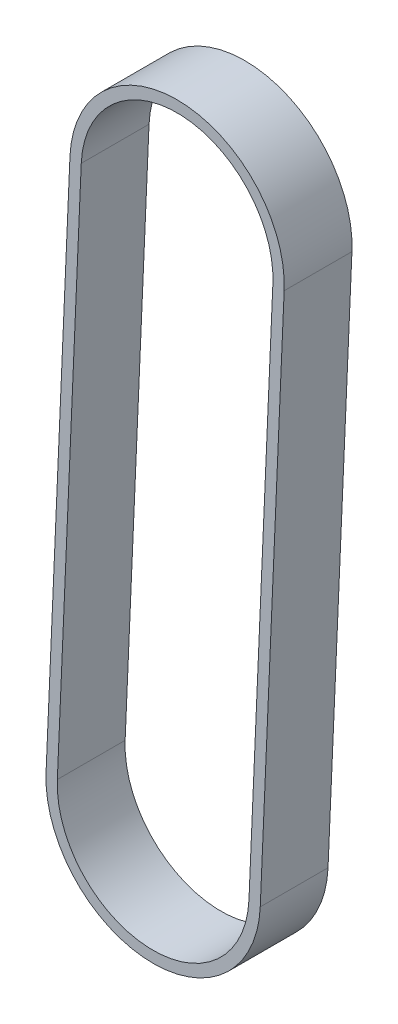
SolidWorks part; units mm, degrees
ref_plane "Front Plane" through (0, 0, 0) normal (0, 0, 1) x (1, 0, 0)
ref_plane "Top Plane" through (0, 0, 0) normal (0, 1, 0) x (1, 0, 0)
ref_plane "Right Plane" through (0, 0, 0) normal (1, 0, 0) x (0, 0, -1)
sketch "Sketch2" plane through (0, 0, 0) normal (0, 0, 1) x (1, 0, 0)
  line L0 (0, 0) -> (1, 0) construction
  line L1 (0, 0) -> (0, 1) construction
  line L2 (12.7202, -0.5576) -> (9.5452, -72.988)
  line L3 (-15.8952, -71.8729) -> (-12.7202, 0.5576)
  arc A0 (-12.7202, 0.5576) -> (12.7202, -0.5576) centre (0, 0) cw
  arc A1 (9.5452, -72.988) -> (-15.8952, -71.8729) centre (-3.175, -72.4304) cw
extrude "Extrude-Thin1" add sketch "Sketch2" along normal blind 9 thin thin type one direction wall 1.5
